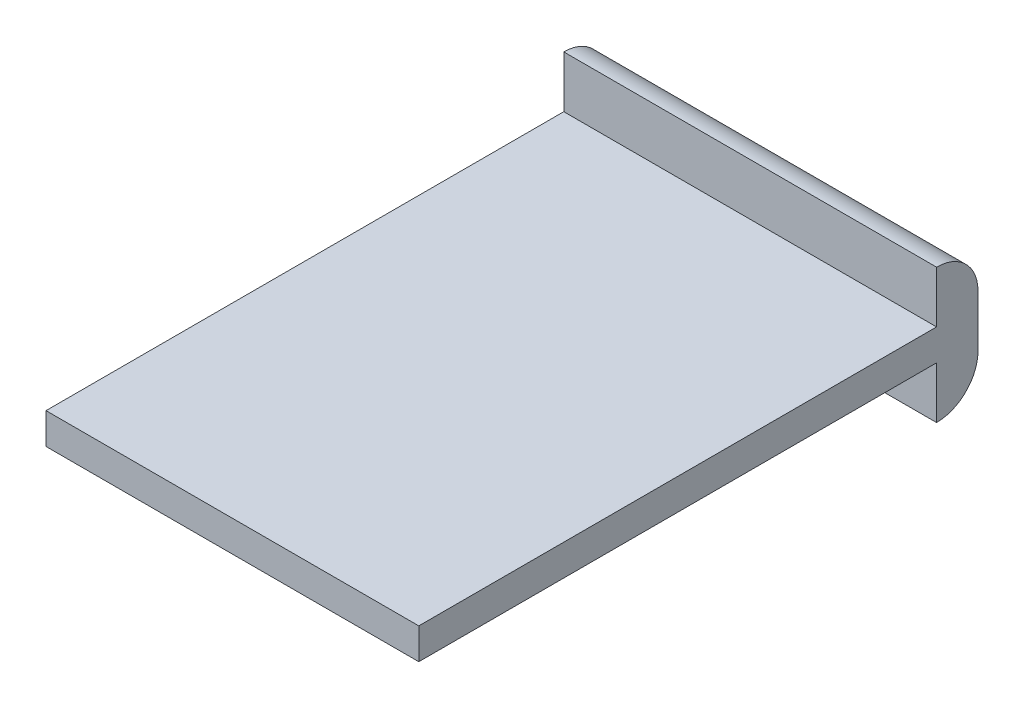
SolidWorks part; units mm, degrees
ref_plane "Front Plane" through (0, 0, 0) normal (0, 0, 1) x (1, 0, 0)
ref_plane "Top Plane" through (0, 0, 0) normal (0, 1, 0) x (1, 0, 0)
ref_plane "Right Plane" through (0, 0, 0) normal (1, 0, 0) x (0, 0, -1)
sketch "Sketch1" plane through (0, 0, 0) normal (0, 1, 0) x (1, 0, 0)
  line L1 (0, 0) -> (18, 0)
  line L2 (0, 0) -> (0, 25)
  line L3 (0, 25) -> (18, 25)
  line L4 (18, 0) -> (18, 25)
  dimension "D1" = 18
  dimension "D2" = 25
extrude "Boss-Extrude1" add sketch "Sketch1" along normal blind 1.5
sketch "Sketch2" plane through (0, 0, -25) normal (0, 0, -1) x (-1, 0, 0)
  line L0 (-18, 0) -> (-18, -2.5)
  line L1 (-18, -2.5) -> (0, -2.5)
  line L2 (0, -2.5) -> (0, 4)
  line L3 (0, 4) -> (-18, 4)
  line L4 (-18, 4) -> (-18, 0)
  dimension "D1" = 2.5
  dimension "D2" = 4
extrude "Boss-Extrude2" add sketch "Sketch2" along normal blind 2
fillet "Fillet1" radius 2 2 edges at (9, 4, -27) (9, -2.5, -27)
